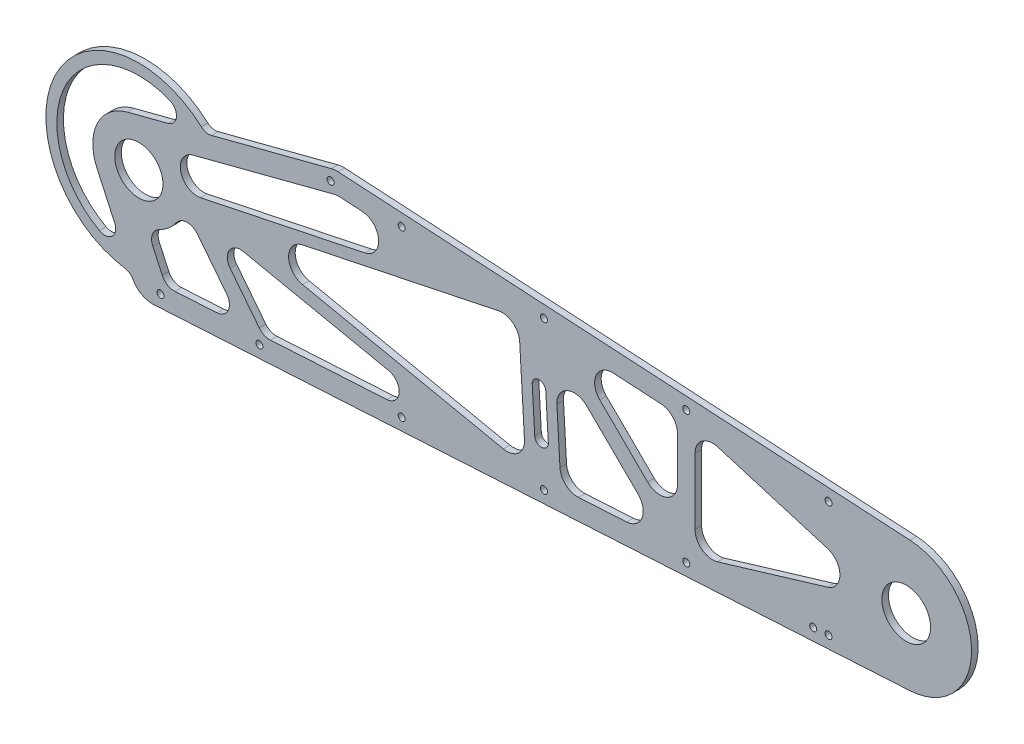
SolidWorks part; units mm, degrees
material "Thornel VCB-20 Carbon Cloth"
ref_plane "Front Plane" through (0, 0, 0) normal (0, 0, 1) x (1, 0, 0)
ref_plane "Top Plane" through (0, 0, 0) normal (0, 1, 0) x (1, 0, 0)
ref_plane "Right Plane" through (0, 0, 0) normal (1, 0, 0) x (0, 0, -1)
sketch "Sketch1" plane through (0, 0, 0) normal (0, 0, 1) x (1, 0, 0)
  line L0 (-175, 0) -> (175, 0) construction
  line L1 (-172.1122, 49.9165) -> (176.7203, 29.7354)
  line L2 (-172.1122, -49.9165) -> (176.7203, -29.7354)
  line L3 (139.566, 26.3757) -> (-120, 41.3925) construction
  line L4 (-55.1085, -37.6383) -> (9.783, -33.8841) construction
  line L5 (-125, 0) -> (-125, 62.9978) construction
  line L6 (-55.5713, 29.6383) -> (-120.4628, 33.3925) construction
  line L7 (-120.4628, 33.3925) -> (-120, 41.3925) construction
  line L8 (-55.5713, 29.6383) -> (-55.1085, 37.6383) construction
  line L9 (-88.0171, 31.5154) -> (-87.5543, 39.5154) construction
  line L10 (-120, -41.3925) -> (-165.1122, -44.0024) construction
  line L11 (139.566, -26.3757) -> (74.6745, -30.1299) construction
  circle A0 centre (175, 0) radius 11.1125
  arc A1 (176.7203, 29.7354) -> (176.7203, -29.7354) centre (175, 0) cw
  circle A3 centre (-175, 0) radius 22.5 construction
  circle A7 centre (-175, 0) radius 11
  circle A9 centre (-120, 41.3925) radius 1.6
  circle A10 centre (-55.1085, 37.6383) radius 1.6
  circle A11 centre (9.783, 33.8841) radius 1.6
  circle A12 centre (74.6745, 30.1299) radius 1.6
  circle A13 centre (139.566, 26.3757) radius 1.6
  circle A15 centre (139.566, -26.3757) radius 1.6
  circle A16 centre (74.6745, -30.1299) radius 1.6
  circle A17 centre (9.783, -33.8841) radius 1.6
  circle A18 centre (-55.1085, -37.6383) radius 1.6
  circle A19 centre (-120, -41.3925) radius 1.6
  arc A20 (-172.1122, 49.9165) -> (-172.1122, -49.9165) centre (-175, 0) ccw
  circle A21 centre (-87.5543, 39.5154) radius 1.6
  circle A22 centre (-165.1122, -44.0024) radius 1.6
  circle A23 centre (-165.1122, 44.0024) radius 1.6
  circle A24 centre (132.5777, -26.78) radius 1.6
  point P4 (0, 0)
  point P18 (-175, 22.5)
  point P21 (-197.5, 0)
  point P22 (-175, -22.5)
  point P23 (-152.5, 0)
  point P30 (-88.0171, 31.5154)
  dimension "D2" = 22.225
  dimension "D3" = 50
  dimension "D5" = 45
  dimension "D6" = 3.2
  dimension "D7" = 260
  dimension "D8" = 5
  dimension "D9" = 7
  dimension "D10" = 22
  dimension "D11" = 7
  dimension "D16" = 5
  dimension "D1" = 350
  dimension "D4" = 8
  dimension "D12" = 5.5
extrude "Boss-Extrude1" add sketch "Sketch1" along normal blind 3
sketch "Sketch4" plane through (0, 0, 3) normal (0, 0, 1) x (1, 0, 0)
  point P10 (-197.5, 0)
  point P13 (-175, 22.5)
  point P16 (-152.5, 0)
  point P19 (-175, -22.5)
hole_wizard "M3 Clearance Hole1" positions "Sketch4" profile "Sketch6" hole size "M3" standard "ANSI Metric" end condition up to next
sketch "Sketch6" plane through (-197.5, 0, 3) normal (1, 0, 0) x (0, -1, 0)
  line L0 (0, 0) -> (0, 3)
  line L1 (0, 3) -> (1.7, 3)
  line L2 (1.7, 3) -> (1.7, 0)
  line L5 (1.7, 0) -> (0, 0)
  line L11 (0, -6.35) -> (0, 107.95) construction
  dimension "Thru Hole Dia." = 3.4
  dimension "Thru Hole Depth" = 3
sketch "Sketch7" plane through (0, 0, 3) normal (0, 0, 1) x (1, 0, 0)
  line L0 (74.6745, 30.1299) -> (74.6745, -30.1299) construction
  line L1 (74.6745, -30.1299) -> (175, 0) construction
  line L2 (175, 0) -> (74.6745, 30.1299) construction
  line L3 (175, 0) -> (-152.5, 0) construction
  line L4 (175, -29.8349) -> (175, 29.8349) construction
  line L5 (88.9755, 22.7026) -> (139.0575, 7.6619)
  line L6 (139.0575, -7.6619) -> (88.9755, -22.7026)
  line L7 (78.6745, -15.0407) -> (78.6745, 15.0407)
  line L8 (9.783, -33.8841) -> (5.5294, 39.6394) construction
  line L9 (9.783, 33.8841) -> (74.6745, -30.1299) construction
  line L10 (9.783, 33.8841) -> (74.6745, 30.1299) construction
  line L11 (9.783, -33.8841) -> (74.6745, -30.1299) construction
  line L12 (-152.5, 0) -> (-55.1085, 37.6383) construction
  line L13 (-55.1085, 37.6383) -> (9.783, 33.8841) construction
  line L14 (9.783, 33.8841) -> (-152.5, 0) construction
  line L15 (70.6745, -1.436) -> (70.6745, 18.8041)
  line L16 (63.1365, 26.7907) -> (41.3408, 28.0517)
  line L17 (35.2605, 14.3698) -> (57.0563, -7.1312)
  line L18 (29.2743, 9.0376) -> (52.6422, -14.0143)
  line L19 (47.486, -27.6962) -> (25.5253, -28.9667)
  line L20 (17.0766, -21.4421) -> (15.6694, 2.8804)
  line L21 (176.7203, 29.7354) -> (-172.1122, 49.9165) construction
  line L22 (-172.1122, -49.9165) -> (176.7203, -29.7354) construction
  line L23 (0.8889, -18.6602) -> (-1.2973, 19.1278)
  line L24 (-10.9191, 26.4969) -> (-100.3161, 7.8311)
  line L25 (-100.3161, -7.8311) -> (-8.7329, -26.9534)
  line L35 (-197.5, 0) -> (-55.1085, 37.6383) construction
  line L52 (-55.1085, -37.6383) -> (-175, -22.5) construction
  line L53 (-15.2425, -47.7117) -> (-52.5586, -43) construction
  line L54 (-0.7058, -39.4678) -> (2.1851, -39.8329) construction
  line L55 (8.6627, -14.5198) -> (7.5076, 5.4468) construction
  line L56 (5.5679, -14.6989) -> (4.4127, 5.2678)
  line L57 (11.7575, -14.3408) -> (10.6024, 5.6258)
  line L58 (176.7203, 29.7354) -> (-172.1122, 49.9165) construction
  line L59 (-175, 22.5) -> (-165.1122, 44.0024) construction
  line L60 (-152.5, 0) -> (-120, 41.3925) construction
  line L61 (-133.3776, 17.8775) -> (-120.0806, 34.8127)
  line L62 (-115.0148, 37.0974) -> (-61.9156, 34.0254)
  line L63 (-61.0358, 22.1621) -> (-127.4321, 8.2988)
  line L64 (-168.6288, 26.7808) -> (-164.3288, 36.1317)
  line L65 (-158.531, 39.6149) -> (-139.3382, 38.5046)
  line L66 (-134.9656, 28.8093) -> (-148.2449, 11.8965)
  line L67 (-179.3293, 22.6595) -> (-175.2558, 31.5179)
  line L68 (-197.5, 0) -> (-225, 0) construction
  line L69 (-208.0189, 4) -> (-200.0799, 4)
  line L70 (-208.0189, -4) -> (-200.0799, -4)
  line L71 (-179.3293, -22.6595) -> (-175.2558, -31.5179)
  line L72 (-168.6288, -26.7808) -> (-164.3288, -36.1317)
  line L73 (-158.531, -39.6149) -> (-139.3382, -38.5046)
  line L74 (-134.9656, -28.8093) -> (-148.2449, -11.8965)
  line L75 (-115.0148, -37.0974) -> (-61.9156, -34.0254)
  line L76 (-133.3776, -17.8775) -> (-120.0806, -34.8127)
  line L77 (-61.0358, -22.1621) -> (-127.4321, -8.2988)
  arc A0 (139.0575, 7.6619) -> (139.0575, -7.6619) centre (136.7565, 0) cw
  arc A1 (88.9755, -22.7026) -> (78.6745, -15.0407) centre (86.6745, -15.0407) cw
  arc A2 (88.9755, 22.7026) -> (78.6745, 15.0407) centre (86.6745, 15.0407) ccw
  arc A3 (70.6745, 18.8041) -> (63.1365, 26.7907) centre (62.6745, 18.8041) ccw
  arc A4 (41.3408, 28.0517) -> (35.2605, 14.3698) centre (40.8787, 20.065) ccw
  arc A5 (70.6745, -1.436) -> (57.0563, -7.1312) centre (62.6745, -1.436) cw
  arc A6 (52.6422, -14.0143) -> (47.486, -27.6962) centre (47.024, -19.7095) cw
  arc A7 (25.5253, -28.9667) -> (17.0766, -21.4421) centre (25.0632, -20.98) cw
  arc A8 (29.2743, 9.0376) -> (15.6694, 2.8804) centre (23.6561, 3.3424) ccw
  arc A9 (0.8889, -18.6602) -> (-8.7329, -26.9534) centre (-7.0978, -19.1222) cw
  arc A10 (-1.2973, 19.1278) -> (-10.9191, 26.4969) centre (-9.2839, 18.6658) ccw
  arc A11 (-100.3161, 7.8311) -> (-100.3161, -7.8311) centre (-98.681, 0) ccw
  circle A30 centre (-175, 0) radius 11 construction
  circle A31 centre (-175, 0) radius 11 construction
  circle A32 centre (-175, 0) radius 22.5 construction
  circle A49 centre (9.783, -33.8841) radius 1.6 construction
  circle A50 centre (9.783, -33.8841) radius 1.6
  circle A52 centre (175, 0) radius 11.1125 construction
  circle A53 centre (175, 0) radius 11.1125 construction
  arc A56 (5.5679, -14.6989) -> (11.7575, -14.3408) centre (8.6627, -14.5198) ccw
  arc A57 (10.6024, 5.6258) -> (4.4127, 5.2678) centre (7.5076, 5.4468) ccw
  circle A58 centre (-165.1122, 44.0024) radius 1.6 construction
  circle A60 centre (-120, 41.3925) radius 1.6 construction
  arc A61 (-157.8609, 12.1348) -> (-165.8048, 18.8798) centre (-175, 0) ccw
  arc A62 (-182.6071, 19.5738) -> (-194.5066, 7.7778) centre (-175, 0) ccw
  arc A63 (-181.6995, 39.942) -> (-213.7614, 11.7391) centre (-175, 0) ccw
  arc A64 (-172.1122, 49.9165) -> (-172.1122, -49.9165) centre (-175, 0) ccw construction
  arc A65 (-175.2558, 31.5179) -> (-181.6995, 39.942) centre (-180.707, 34.0247) ccw
  arc A66 (-213.7614, 11.7391) -> (-208.0189, 4) centre (-208.0189, 10) ccw
  arc A67 (-194.5066, 7.7778) -> (-200.0799, 4) centre (-200.0799, 10) cw
  arc A68 (-182.6071, 19.5738) -> (-179.3293, 22.6595) centre (-184.7806, 25.1663) ccw
  arc A69 (-61.9156, 34.0254) -> (-61.0358, 22.1621) centre (-62.2621, 28.0354) cw
  arc A70 (-120.0806, 34.8127) -> (-115.0148, 37.0974) centre (-115.3614, 31.1074) cw
  arc A71 (-133.3776, 17.8775) -> (-127.4321, 8.2988) centre (-128.6584, 14.1721) ccw
  arc A72 (-139.3382, 38.5046) -> (-134.9656, 28.8093) centre (-139.6847, 32.5146) cw
  arc A73 (-164.3288, 36.1317) -> (-158.531, 39.6149) centre (-158.8776, 33.625) cw
  arc A74 (-165.8048, 18.8798) -> (-168.6288, 26.7808) centre (-163.1776, 24.2741) cw
  arc A75 (-157.8609, 12.1348) -> (-148.2449, 11.8965) centre (-152.9641, 15.6018) ccw
  arc A76 (-213.7614, -11.7391) -> (-208.0189, -4) centre (-208.0189, -10) cw
  arc A77 (-194.5066, -7.7778) -> (-200.0799, -4) centre (-200.0799, -10) ccw
  arc A78 (-182.6071, -19.5738) -> (-194.5066, -7.7778) centre (-175, 0) cw
  arc A79 (-181.6995, -39.942) -> (-213.7614, -11.7391) centre (-175, 0) cw
  arc A80 (-182.6071, -19.5738) -> (-179.3293, -22.6595) centre (-184.7806, -25.1663) cw
  arc A81 (-175.2558, -31.5179) -> (-181.6995, -39.942) centre (-180.707, -34.0247) cw
  arc A82 (-164.3288, -36.1317) -> (-158.531, -39.6149) centre (-158.8776, -33.625) ccw
  arc A83 (-165.8048, -18.8798) -> (-168.6288, -26.7808) centre (-163.1776, -24.2741) ccw
  arc A84 (-157.8609, -12.1348) -> (-165.8048, -18.8798) centre (-175, 0) cw
  arc A85 (-157.8609, -12.1348) -> (-148.2449, -11.8965) centre (-152.9641, -15.6018) cw
  arc A86 (-139.3382, -38.5046) -> (-134.9656, -28.8093) centre (-139.6847, -32.5146) ccw
  arc A87 (-61.9156, -34.0254) -> (-61.0358, -22.1621) centre (-62.2621, -28.0354) ccw
  arc A88 (-120.0806, -34.8127) -> (-115.0148, -37.0974) centre (-115.3614, -31.1074) ccw
  arc A89 (-133.3776, -17.8775) -> (-127.4321, -8.2988) centre (-128.6584, -14.1721) cw
  point P36 (164.5699, 0)
  point P59 (-137.8221, 0)
  point P102 (-15.2425, -47.7117)
  point P126 (8.0851, -4.5365)
  dimension "D8" = 8
  dimension "D11" = 10
  dimension "D12" = 5
  dimension "D20" = 3.1
  dimension "D10" = 4
  dimension "D17" = 6
  dimension "D1" = 3
  dimension "D3" = 8
  dimension "D4" = 8
  dimension "D5" = 8
  dimension "D6" = 16
  dimension "D7" = 6
  dimension "D9" = 8
  dimension "D13" = 8
  dimension "D14" = 5
  dimension "D15" = 8
  dimension "D16" = 24.8967
  dimension "D22" = 20
extrude "Cut-Extrude1" cut sketch "Sketch7" against normal blind 10 contours L57 A57 L56 A56 | L24 A11 L25 A9 L23 A10 | L18 A8 L20 A7 L19 A6 | A89 L76 A88 L75 A87 L77 | L20 A8 L18 A6 L19 A7 | L17 A5 L15 A3 L16 A4 | L7 A2 L5 A0 L6 A1 | L75 A87 L77 A89 L76 A88 | A82 L73 A86 L74 A85 A84 A83 L72 region at (32.1755, -11.823, 3) region at (-42.4165, -0.2065, 3) region at (8.0851, -4.5365, 3) region at (-98.5963, -24.3683, 3)
sketch "Sketch9" [suppressed] plane through (0, 0, 3) normal (0, 0, 1) x (1, 0, 0)
  line L2 (176.7203, 29.7354) -> (-172.1122, 49.9165) construction
  line L3 (-172.1122, -49.9165) -> (176.7203, -29.7354) construction
  line L4 (254.5375, 0) -> (208, 0) construction
  line L5 (200.557, 2) -> (203.931, 2)
  line L6 (200.557, -2) -> (203.931, -2)
  line L7 (162.9445, 26.3755) -> (155.7345, 26.7926)
  line L8 (162.9445, -26.3755) -> (155.7345, -26.7926)
  arc A1 (155.7345, -26.7926) -> (155.7345, 26.7926) centre (175, 0) ccw
  arc A2 (176.7203, -29.7354) -> (176.7203, 29.7354) centre (175, 0) ccw construction
  arc A3 (200.557, -2) -> (200.557, 2) centre (175, 0) ccw
  arc A4 (162.9445, 26.3755) -> (203.931, 2) centre (175, 0) cw
  arc A5 (203.931, -2) -> (162.9445, -26.3755) centre (175, 0) cw
  dimension "D1" = 33
  dimension "D2" = 4
  dimension "D3" = 4
extrude "Boss-Extrude2" [suppressed] add sketch "Sketch9" against normal up to surface (3 mm away) up to face at (56.1489, 13.0862, 0)
fillet "Fillet1" [suppressed] radius 1
fillet "Fillet2" [suppressed] radius 80
sketch "Sketch10" plane through (0, 0, 3) normal (0, 0, 1) x (1, 0, 0)
  line L0 (-165.1122, 44.0024) -> (-120, 41.3925) construction
  line L1 (-165.1122, 44.0024) -> (-210.2243, 46.6123) construction
  line L2 (-172.1122, 49.9165) -> (-210.905, 52.1608)
  line L3 (176.7203, 29.7354) -> (-172.1122, 49.9165) construction
  line L4 (-216.1854, 47.458) -> (-217.3977, 26.5035)
  line L5 (-172.1122, 49.9165) -> (-217.3977, 26.5035)
  circle A0 centre (-120, 41.3925) radius 1.6 construction
  circle A1 centre (-165.1122, 44.0024) radius 1.6 construction
  circle A2 centre (-210.2243, 46.6123) radius 1.6
  arc A3 (-172.1122, 49.9165) -> (-172.1122, -49.9165) centre (-175, 0) ccw construction
  arc A4 (-210.905, 52.1608) -> (-216.1854, 47.458) centre (-211.1938, 47.1692) ccw
  dimension "D2" = 5
  dimension "D1" = 6
extrude "Boss-Extrude3" [suppressed] add sketch "Sketch10" against normal up to surface (3 mm away) up to face at (56.1489, 13.0862, 0)
mirror "Mirror1" [suppressed] about plane through (0, 0, 0) normal (0, 1, 0)
sketch "Sketch13" plane through (0, 0, 3) normal (0, 0, 1) x (1, 0, 0)
  circle A1 centre (-120, 41.3925) radius 1.6 construction
  circle A2 centre (-165.1122, 44.0024) radius 1.6 construction
  circle A3 centre (-152.5, 0) radius 1.7 construction
  circle A4 centre (-175, 22.5) radius 1.7 construction
  circle A5 centre (-197.5, 0) radius 1.7 construction
  circle A6 centre (-175, -22.5) radius 1.7 construction
  circle A8 centre (-120, 41.3925) radius 1.6
  circle A9 centre (-165.1122, 44.0024) radius 1.6
  circle A10 centre (-152.5, 0) radius 1.7
  circle A11 centre (-175, 22.5) radius 1.7
  circle A12 centre (-197.5, 0) radius 1.7
  circle A13 centre (-175, -22.5) radius 1.7
extrude "Boss-Extrude4" add sketch "Sketch13" against normal up to surface (3 mm away) up to face at (56.1489, 13.0862, 0)
sketch "Sketch12" plane through (0, 0, 0) normal (0, 0, 1) x (1, 0, 0)
  line L0 (176.7203, 29.7354) -> (-172.1122, 49.9165) construction
  line L1 (-180.2821, 20.3249) -> (-85.6614, 44.9151)
  line L2 (176.7203, 29.7354) -> (-172.1122, 49.9165) construction
  line L3 (-175.1216, -49.9999) -> (-194.0794, -8.7736)
  line L4 (-168.6288, -26.7808) -> (-164.3288, -36.1317) construction
  line L5 (-172.1122, 49.9165) -> (-85.6614, 44.9151)
  line L6 (-150.3194, 18.2961) -> (-85.9362, 35.0281)
  line L7 (-146.7921, 3.2349) -> (-71.9712, 18.8573)
  line L9 (-10.9191, 26.4969) -> (-100.3161, 7.8311) construction
  line L10 (-83.4619, 35.2719) -> (-73.1442, 34.675)
  line L11 (63.1365, 26.7907) -> (41.3408, 28.0517) construction
  line L12 (-191.9615, 12.3818) -> (-87.5543, 39.5154) construction
  arc A0 (-194.0794, -8.7736) -> (-180.2821, 20.3249) centre (-175, 0) cw
  arc A1 (-71.9712, 18.8573) -> (-73.1442, 34.675) centre (-73.6063, 26.6884) ccw
  arc A2 (-85.9362, 35.0281) -> (-83.4619, 35.2719) centre (-83.924, 27.2853) cw
  arc A3 (-172.1122, 49.9165) -> (-172.1122, -49.9165) centre (-175, 0) ccw construction
  circle A4 centre (-175, 0) radius 11 construction
  arc A6 (-175.1216, -49.9999) -> (-172.1122, 49.9165) centre (-175, 0) cw
  arc A7 (-172.1122, 49.9165) -> (-172.1122, -49.9165) centre (-175, 0) ccw construction
  circle A13 centre (-87.5543, 39.5154) radius 1.6 construction
  arc A14 (-150.3194, 18.2961) -> (-146.7921, 3.2349) centre (-148.3734, 10.8082) ccw
  arc A15 (-157.8609, -12.1348) -> (-180.2821, 20.3249) centre (-175, 0) ccw construction
  dimension "D1" = 10
  dimension "D5" = 8
  dimension "D3" = 9.5
  dimension "D4" = 5
extrude "Cut-Extrude2" cut sketch "Sketch12" against normal through all both and the other way through all
fillet "Fillet3" radius 10 2 edges at (-85.6614, 44.9151, 1.5) (-175.1216, -49.9999, 1.5)
sketch "Sketch14" plane through (0, 0, 0) normal (0, 0, -1) x (-1, 0, 0)
  line L0 (177.9317, -43.8888) -> (194.0794, -8.7736) construction
  line L1 (180.2821, 20.3249) -> (87.1839, 44.5194) construction
  line L2 (181.1497, -36.8909) -> (178.6903, -42.2391)
  line L3 (150.3293, 28.109) -> (144.6321, 29.5897)
  arc A0 (181.1497, -36.8909) -> (150.3293, 28.109) centre (175, 0) ccw
  arc A1 (178.6903, -42.2391) -> (144.6321, 29.5897) centre (175, 0) ccw
  circle A2 centre (175, 0) radius 11 construction
  circle A3 centre (175, 0) radius 11 construction
  dimension "D1" = 42.4
  dimension "D2" = 5
extrude "Boss-Extrude5" add sketch "Sketch14" against normal up to surface (3 mm away) up to face at (-64.7542, 1.1454, 3)
fillet "Fillet4" radius 5 4 edges at (-178.6903, -42.2391, 1.5) (-181.1497, -36.8909, 1.5) (-144.6321, 29.5897, 1.5) (-150.3293, 28.109, 1.5)
